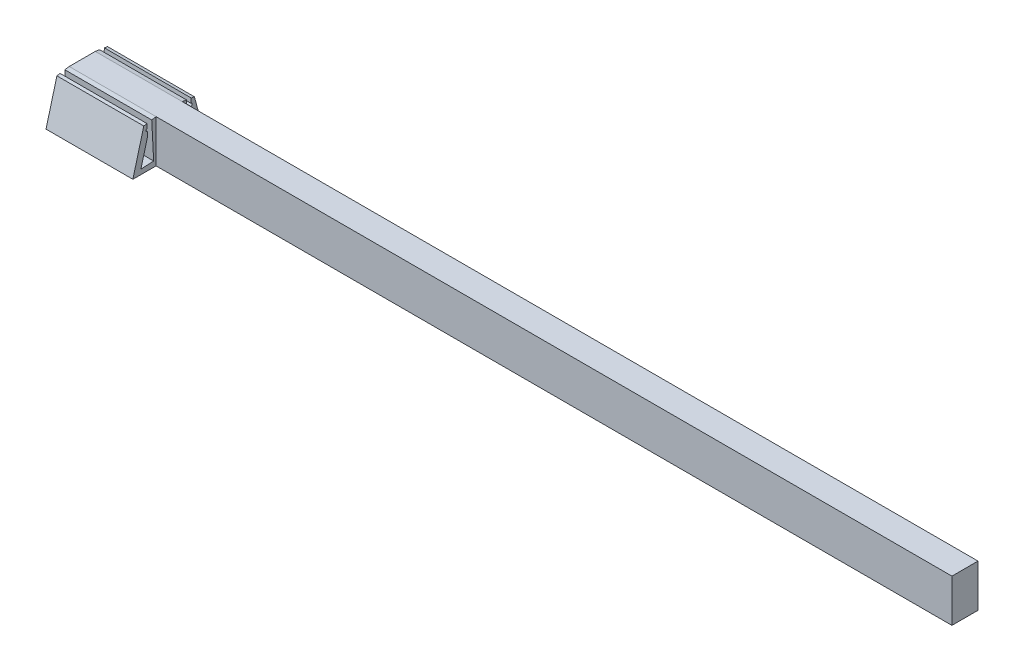
SolidWorks part; units mm, degrees
ref_plane "Front Plane" through (0, 0, 0) normal (0, 0, 1) x (1, 0, 0)
ref_plane "Top Plane" through (0, 0, 0) normal (0, 1, 0) x (1, 0, 0)
ref_plane "Right Plane" through (0, 0, 0) normal (1, 0, 0) x (0, 0, -1)
sketch "Sketch1" plane through (0, 0, 0) normal (1, 0, 0) x (0, 0, -1)
  line L0 (3.6311, 0.3059) -> (9.4677, 0) construction
  line L1 (3.904, 5.5131) -> (4.9077, 5.4605) construction
  line L2 (6.2203, 9.4885) -> (6.0816, 6.8415) construction
  line L3 (6.0816, 6.8415) -> (7.6191, 1.1033)
  line L4 (7.6191, 1.1033) -> (4.6874, 1.2569)
  line L5 (4.6874, 1.2569) -> (5.128, 9.664)
  line L6 (5.128, 9.664) -> (4.13, 9.8243)
  line L7 (4.13, 9.8243) -> (3.6311, 0.3059) construction
  line L8 (6.2203, 9.4885) -> (6.1666, 8.4646)
  line L9 (6.1352, 7.8654) -> (6.0816, 6.8415)
  line L10 (6.2203, 9.4885) -> (6.9569, 9.3702)
  line L11 (6.9569, 9.3702) -> (9.4677, 0)
  line L12 (6.1532, 1.1801) -> (6.1006, 0.1765) construction
  line L13 (1.128, 0) -> (1.128, 7.6812) construction
  line L14 (-3.8973, 1.1801) -> (-3.8447, 0.1765) construction
  line L15 (-5.3632, 1.1033) -> (-2.4314, 1.2569)
  line L16 (-3.9644, 9.4885) -> (-3.8256, 6.8415) construction
  line L17 (-1.6481, 5.5131) -> (-2.6517, 5.4605) construction
  line L18 (-1.3752, 0.3059) -> (-7.2117, 0) construction
  line L19 (-4.701, 9.3702) -> (-7.2117, 0)
  line L20 (-3.9644, 9.4885) -> (-4.701, 9.3702)
  line L21 (-3.8793, 7.8654) -> (-3.8256, 6.8415)
  line L22 (-3.9644, 9.4885) -> (-3.9107, 8.4646)
  line L23 (-1.874, 9.8243) -> (-1.3752, 0.3059) construction
  line L24 (-2.872, 9.664) -> (-1.874, 9.8243)
  line L25 (-2.4314, 1.2569) -> (-2.872, 9.664)
  line L26 (-3.8256, 6.8415) -> (-5.3632, 1.1033)
  line L27 (-1.874, 9.8243) -> (4.13, 9.8243)
  line L28 (-7.2117, 0) -> (-2.3656, 0)
  line L29 (-2.4314, 1.2569) -> (-2.3656, 0)
  line L30 (4.6874, 1.2569) -> (4.6215, 0)
  line L31 (-2.3656, 0) -> (4.6215, 0)
  line L32 (4.6215, 0) -> (9.4677, 0)
  arc A0 (6.1666, 8.4646) -> (6.1352, 7.8654) centre (6.1509, 8.165) cw
  arc A1 (-3.9107, 8.4646) -> (-3.8793, 7.8654) centre (-3.895, 8.165) ccw
  dimension "D1" = 0.3
  dimension "D2" = 1.1
  dimension "D3" = 72
  dimension "D4" = 1.5
  dimension "D5" = 8
extrude "Clip #1" add sketch "Sketch1" along normal blind 20 contours L28 L19 L20 L22 A1 L21 L26 L15 L25 L24 L27 L6 L5 L4 L3 L9 A0 L8 L10 L11 L32 L31
sketch "Sketch4" plane through (0, 0, 0) normal (1, 0, 0) x (0, 0, -1)
  line L0 (-1.874, 9.8243) -> (-1.874, 0)
  line L1 (-2.3656, 0) -> (4.6215, 0) construction
  line L2 (-1.874, 9.8243) -> (4.13, 9.8243)
  line L3 (4.13, 9.8243) -> (4.13, 0)
  line L4 (4.13, 0) -> (-1.874, 0)
extrude "Center beam" add sketch "Sketch4" along normal blind 203.2
